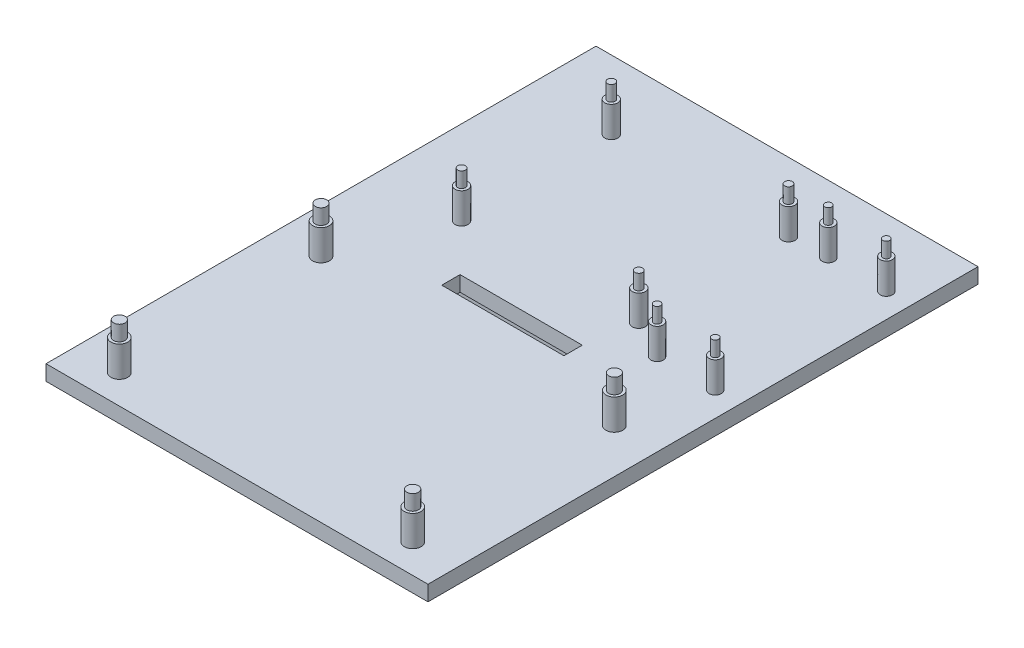
SolidWorks part; units mm, degrees
ref_plane "Front" through (0, 0, 0) normal (0, 0, 1) x (1, 0, 0)
ref_plane "Top" through (0, 0, 0) normal (0, 1, 0) x (1, 0, 0)
ref_plane "Right" through (0, 0, 0) normal (1, 0, 0) x (0, 0, -1)
sketch "Esquisse1" plane through (0, 0, 0) normal (0, 1, 0) x (1, 0, 0)
  line L1 (-31, 6) -> (31, 6)
  line L2 (-31, 6) -> (-31, -6)
  line L3 (-31, -6) -> (31, -6)
  line L4 (31, 6) -> (31, -6)
  line L5 (-31, 6) -> (31, -6) construction
  line L6 (-31, -6) -> (31, 6) construction
  line L7 (-29, 4) -> (29, 4)
  line L8 (-29, 4) -> (-29, -4)
  line L9 (-29, -4) -> (29, -4)
  line L10 (29, 4) -> (29, -4)
  line L11 (-29, 4) -> (29, -4) construction
  line L12 (-29, -4) -> (29, 4) construction
  point P0 (0, 0)
  point P6 (0, 0)
  dimension "D1" = 8
  dimension "D2" = 12
  dimension "D3" = 62
  dimension "D4" = 58
extrude "Boss.-Extru.1" add sketch "Esquisse1" along normal blind 15
sketch "Esquisse2" plane through (0, 0, 6) normal (0, 0, 1) x (1, 0, 0)
  line L0 (-31, 15) -> (31, 15) construction
  line L1 (31, 15) -> (31, 0) construction
  circle A0 centre (0, 9) radius 3.175
  dimension "D1" = 6.35
  dimension "D2" = 6
  dimension "D3" = 31
extrude "Enlèv. mat.-Extru.1" cut sketch "Esquisse2" against normal through all
sketch "Esquisse3" plane through (0, 15, 0) normal (0, 1, 0) x (1, 0, 0)
  line L1 (-62.5, 90) -> (62.5, 90)
  line L2 (-62.5, 90) -> (-62.5, -90)
  line L3 (-62.5, -90) -> (62.5, -90)
  line L4 (62.5, 90) -> (62.5, -90)
  line L5 (-62.5, 90) -> (62.5, -90) construction
  line L6 (-62.5, -90) -> (62.5, 90) construction
  point P0 (0, 0)
  dimension "D1" = 180
  dimension "D2" = 125
extrude "Boss.-Extru.2" add sketch "Esquisse3" along normal blind 5
sketch "Esquisse4" plane through (0, 20, 0) normal (0, 1, 0) x (1, 0, 0)
  line L0 (62.5, -90) -> (62.5, 90) construction
  line L1 (-52.5, -85) -> (52.5, -85) construction
  line L2 (-52.5, -85) -> (-52.5, -10) construction
  line L3 (-52.5, -10) -> (52.5, -10) construction
  line L4 (52.5, -85) -> (52.5, -10) construction
  line L5 (-52.5, -85) -> (52.5, -10) construction
  line L6 (-52.5, -10) -> (52.5, -85) construction
  line L7 (-62.5, -90) -> (62.5, -90) construction
  line L8 (-62.5, 90) -> (-62.5, -90) construction
  line L9 (-57.5, 15) -> (26.5, 15) construction
  line L10 (-57.5, 15) -> (-57.5, 71) construction
  line L11 (-57.5, 71) -> (26.5, 71) construction
  line L12 (26.5, 15) -> (26.5, 71) construction
  line L13 (-57.5, 15) -> (26.5, 71) construction
  line L14 (-57.5, 71) -> (26.5, 15) construction
  line L15 (32.5, 9) -> (57.5, 9) construction
  line L16 (32.5, 9) -> (32.5, 71) construction
  line L17 (32.5, 71) -> (57.5, 71) construction
  line L18 (57.5, 9) -> (57.5, 71) construction
  line L19 (32.5, 9) -> (57.5, 71) construction
  line L20 (32.5, 71) -> (57.5, 9) construction
  point P4 (0, -47.5)
  point P10 (0, -90)
  point P15 (-15.5, 43)
  point P21 (45, 40)
  point P22 (62.5, 0)
  dimension "D1" = 75
  dimension "D2" = 105
  dimension "D3" = 5
  dimension "D4" = 56
  dimension "D5" = 84
  dimension "D6" = 5
  dimension "D7" = 62
  dimension "D8" = 25
  dimension "D9" = 5
  dimension "D10" = 15
sketch "Esquisse6" plane through (0, 15, 0) normal (0, -1, 0) x (-1, 0, 0)
  line L0 (-29, -4) -> (-29, 4) construction
  line L1 (20, 3) -> (-20, 3)
  line L2 (20, 3) -> (20, -3)
  line L3 (20, -3) -> (-20, -3)
  line L4 (-20, 3) -> (-20, -3)
  line L5 (20, 3) -> (-20, -3) construction
  line L6 (20, -3) -> (-20, 3) construction
  line L7 (29, -4) -> (-29, -4) construction
  point P4 (0, 0)
  point P8 (-29, 0)
  point P12 (0, -4)
  dimension "D1" = 6
  dimension "D2" = 40
extrude "Enlèv. mat.-Extru.3" cut sketch "Esquisse6" against normal up to next
sketch "Esquisse8" plane through (0, 20, 0) normal (0, 1, 0) x (1, 0, 0)
  line L0 (-57.5, 71) -> (26.5, 71) construction
  line L1 (26.5, 15) -> (26.5, 71) construction
  circle A0 centre (23, 67.5) radius 1.25
  circle A1 centre (23, 18.5) radius 1.25
  circle A2 centre (-35, 67.5) radius 1.25
  circle A3 centre (-35, 18.5) radius 1.25
  point P8 (0, 0)
  point P13 (0, 0)
  dimension "D1" = 2.5
  dimension "D4" = 2.5
  dimension "D6" = 2.5
  dimension "D8" = 2.5
  dimension "D2" = 3.5
  dimension "D3" = 3.5
  dimension "D5" = 49
  dimension "D7" = 58
sketch "Esquisse9" plane through (0, 20, 0) normal (0, 1, 0) x (1, 0, 0)
  line L0 (57.5, 9) -> (57.5, 71) construction
  line L1 (32.5, 71) -> (57.5, 71) construction
  circle A0 centre (54.5, 68) radius 1.125
  circle A1 centre (35.5, 68) radius 1.125
  circle A2 centre (54.5, 12) radius 1.125
  circle A3 centre (35.5, 12) radius 1.125
  dimension "D1" = 2.25
  dimension "D4" = 2.25
  dimension "D6" = 2.25
  dimension "D8" = 2.25
  dimension "D2" = 3
  dimension "D3" = 3
  dimension "D5" = 19
  dimension "D7" = 56
sketch "Esquisse10" plane through (0, 20, 0) normal (0, 1, 0) x (1, 0, 0)
  line L0 (-52.5, -10) -> (52.5, -10) construction
  line L1 (-52.5, -85) -> (-52.5, -10) construction
  circle A0 centre (-48, -14.5) radius 1.875
  circle A1 centre (48, -14.5) radius 1.875
  circle A2 centre (-48, -80.5) radius 1.875
  circle A3 centre (48, -80.5) radius 1.875
  point P10 (0, 0)
  dimension "D1" = 3.75
  dimension "D4" = 3.75
  dimension "D6" = 3.75
  dimension "D8" = 3.75
  dimension "D2" = 4.5
  dimension "D3" = 4.5
  dimension "D5" = 96
  dimension "D7" = 66
sketch "Esquisse11" plane through (0, 20, 0) normal (0, 1, 0) x (1, 0, 0)
  line L0 (-52.5, -10) -> (52.5, -10) construction
  line L1 (-52.5, -85) -> (-52.5, -10) construction
  circle A0 centre (-48, -14.5) radius 2.75
  circle A1 centre (-48, -80.5) radius 2.75
  circle A2 centre (48, -14.5) radius 2.75
  circle A3 centre (48, -80.5) radius 2.75
  point P8 (0, 0)
  dimension "D3" = 5.5
  dimension "D5" = 5.5
  dimension "D6" = 96
  dimension "D7" = 5.5
  dimension "D8" = 5.5
  dimension "D1" = 4.5
  dimension "D2" = 4.5
  dimension "D4" = 66
sketch "Esquisse12" plane through (0, 20, 0) normal (0, 1, 0) x (1, 0, 0)
  line L0 (-57.5, 71) -> (26.5, 71) construction
  line L1 (26.5, 15) -> (26.5, 71) construction
  circle A0 centre (23, 67.5) radius 2.125
  circle A1 centre (23, 18.5) radius 2.125
  circle A2 centre (-35, 67.5) radius 2.125
  circle A3 centre (-35, 18.5) radius 2.125
  point P8 (0, 0)
  point P13 (0, 0)
  dimension "D3" = 4.25
  dimension "D5" = 4.25
  dimension "D7" = 4.25
  dimension "D8" = 4.25
  dimension "D1" = 3.5
  dimension "D2" = 3.5
  dimension "D4" = 49
  dimension "D6" = 58
sketch "Esquisse13" plane through (0, 20, 0) normal (0, 1, 0) x (1, 0, 0)
  line L0 (32.5, 9) -> (57.5, 9) construction
  line L1 (57.5, 9) -> (57.5, 71) construction
  circle A0 centre (54.5, 12) radius 2
  circle A1 centre (54.5, 68) radius 2
  circle A2 centre (35.5, 12) radius 2
  circle A3 centre (35.5, 68) radius 2
  point P8 (0, 0)
  point P13 (0, 0)
  dimension "D3" = 4
  dimension "D4" = 4
  dimension "D6" = 4
  dimension "D8" = 4
  dimension "D1" = 3
  dimension "D2" = 3
  dimension "D5" = 56
  dimension "D7" = 19
extrude "Boss.-Extru.3" add sketch "Esquisse11" along normal blind 10
extrude "Boss.-Extru.4" add sketch "Esquisse13" along normal blind 10
extrude "Boss.-Extru.5" add sketch "Esquisse12" along normal blind 10
extrude "Boss.-Extru.6" add sketch "Esquisse10" along normal blind 15
extrude "Boss.-Extru.7" add sketch "Esquisse9" along normal blind 15
extrude "Boss.-Extru.8" add sketch "Esquisse8" along normal blind 15
